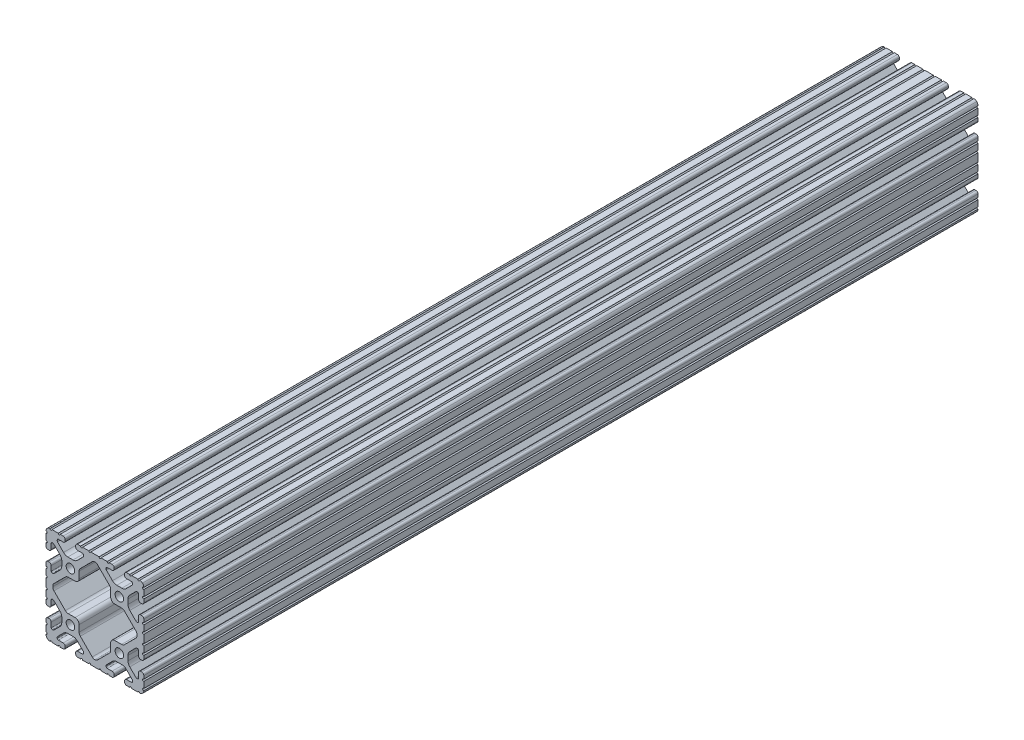
SolidWorks part; units mm, degrees
ref_plane "Front Plane" through (0, 0, 0) normal (0, 0, 1) x (1, 0, 0)
ref_plane "Top Plane" through (0, 0, 0) normal (0, 1, 0) x (1, 0, 0)
ref_plane "Right Plane" through (0, 0, 0) normal (1, 0, 0) x (0, 0, -1)
sketch "Sketch1" plane through (0, 0, 0) normal (0, 0, 1) x (1, 0, 0)
  line L0 (0, 38.1) -> (0, -38.1) construction
  line L1 (-38.1, -38.1) -> (38.1, -38.1) construction
  line L2 (-38.1, -38.1) -> (-38.1, 38.1) construction
  line L3 (-38.1, 38.1) -> (38.1, 38.1) construction
  line L4 (38.1, -38.1) -> (38.1, 38.1) construction
  line L5 (0, 38.1) -> (0, -38.1) construction
  line L6 (-38.1, 0) -> (38.1, 0) construction
  line L7 (-19.05, 19.05) -> (19.05, 19.05) construction
  line L8 (-19.05, 19.05) -> (-19.05, -19.05) construction
  line L9 (-19.05, -19.05) -> (19.05, -19.05) construction
  line L10 (19.05, 19.05) -> (19.05, -19.05) construction
  line L11 (-23.114, 38.1) -> (-23.114, -38.1) construction
  line L12 (-23.114, -38.1) -> (-14.986, 38.1) construction
  line L13 (-14.986, 38.1) -> (-14.986, -38.1) construction
  circle A0 centre (19.05, 19.05) radius 3.3274
  point P0 (0, 0)
  point P9 (0, 0)
  point P12 (-19.05, 0)
  line B0 (-11.3637, -22.8433) -> (-2.0515, -32.1555)
  line B1 (-12.2936, -15.4686) -> (-12.2936, -20.5983)
  line B2 (-20.769, -12.2936) -> (-15.4686, -12.2936)
  line B3 (-31.9021, -2.4756) -> (-23.0141, -11.3637)
  line B4 (-23.0141, 11.3637) -> (-31.9021, 2.4756)
  line B5 (-15.4686, 12.2936) -> (-20.769, 12.2936)
  line B6 (-12.2936, 20.5983) -> (-12.2936, 15.4686)
  line B7 (-2.0515, 32.1555) -> (-11.3637, 22.8433)
  line B8 (11.3637, 22.8433) -> (2.0515, 32.1555)
  line B9 (12.2936, 15.4686) -> (12.2936, 20.5983)
  line B10 (20.769, 12.2936) -> (15.4686, 12.2936)
  line B11 (31.9021, 2.4756) -> (23.0141, 11.3637)
  line B12 (23.0141, -11.3637) -> (31.9021, -2.4756)
  line B13 (15.4686, -12.2936) -> (20.769, -12.2936)
  line B14 (12.2936, -20.5983) -> (12.2936, -15.4686)
  line B15 (2.0515, -32.1555) -> (11.3637, -22.8433)
  line B16 (-4.7773, 38.1) -> (-9.6053, 38.1)
  line B17 (-11.1289, 38.1) -> (-13.4112, 38.1)
  line B18 (-14.986, 36.5252) -> (-14.986, 35.6108)
  line B19 (-13.4112, 34.036) -> (-9.652, 34.036)
  line B20 (-8.763, 33.147) -> (-8.763, 32.4935)
  line B21 (-9.0234, 31.8649) -> (-13.6907, 27.1976)
  line B22 (-17.0493, 25.8064) -> (-21.0507, 25.8064)
  line B23 (-24.4093, 27.1976) -> (-29.1002, 31.8885)
  line B24 (-29.337, 32.7207) -> (-29.337, 33.147)
  line B25 (-28.448, 34.036) -> (-24.6888, 34.036)
  line B26 (-23.114, 35.6108) -> (-23.114, 36.5252)
  line B27 (-24.6888, 38.1) -> (-27.0772, 38.1)
  line B28 (-28.6011, 38.1) -> (-33.4288, 38.1)
  line B29 (-38.1, 33.373) -> (-38.1, 28.5453)
  line B30 (-38.1, 27.0238) -> (-38.1, 24.6302)
  line B31 (-36.5252, 23.0554) -> (-35.6108, 23.0554)
  line B32 (-34.036, 24.6302) -> (-34.036, 28.448)
  line B33 (-33.147, 29.337) -> (-32.6643, 29.337)
  line B34 (-32.0357, 29.0766) -> (-27.1976, 24.2385)
  line B35 (-25.8064, 20.8799) -> (-25.8064, 17.2201)
  line B36 (-27.1976, 13.8615) -> (-31.9489, 9.1101)
  line B37 (-32.7869, 8.763) -> (-33.0603, 8.763)
  line B38 (-34.036, 9.7387) -> (-34.036, 13.4698)
  line B39 (-35.6108, 15.0446) -> (-36.5252, 15.0446)
  line B40 (-38.1, 13.4698) -> (-38.1, 11.075)
  line B41 (-38.1, 9.552) -> (-38.1, 4.7238)
  line B42 (-38.1, 3.2007) -> (-38.1, -3.2007)
  line B43 (-38.1, -4.7238) -> (-38.1, -9.552)
  line B44 (-38.1, -11.075) -> (-38.1, -13.4698)
  line B45 (-36.5252, -15.0446) -> (-35.6108, -15.0446)
  line B46 (-34.036, -13.4698) -> (-34.036, -9.7387)
  line B47 (-33.0603, -8.763) -> (-32.7869, -8.763)
  line B48 (-31.9489, -9.1101) -> (-27.1976, -13.8615)
  line B49 (-25.8064, -17.2201) -> (-25.8064, -20.8799)
  line B50 (-27.1976, -24.2385) -> (-32.0357, -29.0766)
  line B51 (-32.6643, -29.337) -> (-33.147, -29.337)
  line B52 (-34.036, -28.448) -> (-34.036, -24.6302)
  line B53 (-35.6108, -23.0554) -> (-36.5252, -23.0554)
  line B54 (-38.1, -24.6302) -> (-38.1, -27.0238)
  line B55 (-38.1, -28.5453) -> (-38.1, -33.373)
  line B56 (-33.4288, -38.1) -> (-28.6011, -38.1)
  line B57 (-27.0772, -38.1) -> (-24.6888, -38.1)
  line B58 (-23.114, -36.5252) -> (-23.114, -35.6108)
  line B59 (-24.6888, -34.036) -> (-28.448, -34.036)
  line B60 (-29.337, -33.147) -> (-29.337, -32.7207)
  line B61 (-29.1002, -31.8885) -> (-24.4093, -27.1976)
  line B62 (-21.0507, -25.8064) -> (-17.0493, -25.8064)
  line B63 (-13.6907, -27.1976) -> (-9.0234, -31.8649)
  line B64 (-8.763, -32.4935) -> (-8.763, -33.147)
  line B65 (-9.652, -34.036) -> (-13.4112, -34.036)
  line B66 (-14.986, -35.6108) -> (-14.986, -36.5252)
  line B67 (-13.4112, -38.1) -> (-11.1289, -38.1)
  line B68 (-9.6053, -38.1) -> (-4.7773, -38.1)
  line B69 (-3.2537, -38.1) -> (3.2537, -38.1)
  line B70 (4.7773, -38.1) -> (9.6053, -38.1)
  line B71 (11.1289, -38.1) -> (13.4112, -38.1)
  line B72 (14.986, -36.5252) -> (14.986, -35.6108)
  line B73 (13.4112, -34.036) -> (9.652, -34.036)
  line B74 (8.763, -33.147) -> (8.763, -32.4935)
  line B75 (9.0234, -31.8649) -> (13.6907, -27.1976)
  line B76 (17.0493, -25.8064) -> (21.0507, -25.8064)
  line B77 (24.4093, -27.1976) -> (29.1002, -31.8885)
  line B78 (29.337, -32.7207) -> (29.337, -33.147)
  line B79 (28.448, -34.036) -> (24.6888, -34.036)
  line B80 (23.114, -35.6108) -> (23.114, -36.5252)
  line B81 (24.6888, -38.1) -> (27.0772, -38.1)
  line B82 (28.6011, -38.1) -> (33.4288, -38.1)
  line B83 (38.1, -33.373) -> (38.1, -28.5453)
  line B84 (38.1, -27.0238) -> (38.1, -24.6302)
  line B85 (36.5252, -23.0554) -> (35.6108, -23.0554)
  line B86 (34.036, -24.6302) -> (34.036, -28.448)
  line B87 (33.147, -29.337) -> (32.6643, -29.337)
  line B88 (32.0357, -29.0766) -> (27.1976, -24.2385)
  line B89 (25.8064, -20.8799) -> (25.8064, -17.2201)
  line B90 (27.1976, -13.8615) -> (31.9489, -9.1101)
  line B91 (32.7869, -8.763) -> (33.0603, -8.763)
  line B92 (34.036, -9.7387) -> (34.036, -13.4698)
  line B93 (35.6108, -15.0446) -> (36.5252, -15.0446)
  line B94 (38.1, -13.4698) -> (38.1, -11.075)
  line B95 (38.1, -9.552) -> (38.1, -4.7238)
  line B96 (38.1, -3.2007) -> (38.1, 3.2007)
  line B97 (38.1, 4.7238) -> (38.1, 9.552)
  line B98 (38.1, 11.075) -> (38.1, 13.4698)
  line B99 (36.5252, 15.0446) -> (35.6108, 15.0446)
  line B100 (34.036, 13.4698) -> (34.036, 9.7387)
  line B101 (33.0603, 8.763) -> (32.7869, 8.763)
  line B102 (31.9489, 9.1101) -> (27.1976, 13.8615)
  line B103 (25.8064, 17.2201) -> (25.8064, 20.8799)
  line B104 (27.1976, 24.2385) -> (32.0357, 29.0766)
  line B105 (32.6643, 29.337) -> (33.147, 29.337)
  line B106 (34.036, 28.448) -> (34.036, 24.6302)
  line B107 (35.6108, 23.0554) -> (36.5252, 23.0554)
  line B108 (38.1, 24.6302) -> (38.1, 27.0238)
  line B109 (38.1, 28.5453) -> (38.1, 33.373)
  line B110 (33.4288, 38.1) -> (28.6011, 38.1)
  line B111 (27.0772, 38.1) -> (24.6888, 38.1)
  line B112 (23.114, 36.5252) -> (23.114, 35.6108)
  line B113 (24.6888, 34.036) -> (28.448, 34.036)
  line B114 (29.337, 33.147) -> (29.337, 32.7207)
  line B115 (29.1002, 31.8885) -> (24.4093, 27.1976)
  line B116 (21.0507, 25.8064) -> (17.0493, 25.8064)
  line B117 (13.6907, 27.1976) -> (9.0234, 31.8649)
  line B118 (8.763, 32.4935) -> (8.763, 33.147)
  line B119 (9.652, 34.036) -> (13.4112, 34.036)
  line B120 (14.986, 35.6108) -> (14.986, 36.5252)
  line B121 (13.4112, 38.1) -> (11.1289, 38.1)
  line B122 (9.6053, 38.1) -> (4.7773, 38.1)
  line B123 (3.2537, 38.1) -> (-3.2537, 38.1)
  circle B124 centre (-19.05, 19.05) radius 3.3274
  circle B125 centre (-19.05, -19.05) radius 3.3274
  circle B126 centre (19.05, -19.05) radius 3.3274
  circle B127 centre (19.05, 19.05) radius 3.3274
  arc B128 (0, -33.011) -> (2.0515, -32.1555) centre (-0.0139, -30.09) ccw
  arc B129 (-2.0515, -32.1555) -> (0, -33.011) centre (0.0139, -30.09) ccw
  arc B130 (-12.2936, -20.5983) -> (-11.3637, -22.8433) centre (-9.1186, -20.5983) ccw
  arc B131 (-12.2936, -15.4686) -> (-15.4686, -12.2936) centre (-15.4686, -15.4686) ccw
  arc B132 (-23.0141, -11.3637) -> (-20.769, -12.2936) centre (-20.769, -9.1186) ccw
  arc B133 (-32.7287, 0) -> (-31.9021, -2.4756) centre (-29.8367, -0.4102) ccw
  arc B134 (-31.9021, 2.4756) -> (-32.7287, 0) centre (-29.8367, 0.4102) ccw
  arc B135 (-20.769, 12.2936) -> (-23.0141, 11.3637) centre (-20.769, 9.1186) ccw
  arc B136 (-15.4686, 12.2936) -> (-12.2936, 15.4686) centre (-15.4686, 15.4686) ccw
  arc B137 (-11.3637, 22.8433) -> (-12.2936, 20.5983) centre (-9.1186, 20.5983) ccw
  arc B138 (0, 33.011) -> (-2.0515, 32.1555) centre (0.0139, 30.09) ccw
  arc B139 (2.0515, 32.1555) -> (0, 33.011) centre (-0.0139, 30.09) ccw
  arc B140 (12.2936, 20.5983) -> (11.3637, 22.8433) centre (9.1186, 20.5983) ccw
  arc B141 (12.2936, 15.4686) -> (15.4686, 12.2936) centre (15.4686, 15.4686) ccw
  arc B142 (23.0141, 11.3637) -> (20.769, 12.2936) centre (20.769, 9.1186) ccw
  arc B143 (32.7287, 0) -> (31.9021, 2.4756) centre (29.8367, 0.4102) ccw
  arc B144 (31.9021, -2.4756) -> (32.7287, 0) centre (29.8367, -0.4102) ccw
  arc B145 (20.769, -12.2936) -> (23.0141, -11.3637) centre (20.769, -9.1186) ccw
  arc B146 (15.4686, -12.2936) -> (12.2936, -15.4686) centre (15.4686, -15.4686) ccw
  arc B147 (11.3637, -22.8433) -> (12.2936, -20.5983) centre (9.1186, -20.5983) ccw
  arc B148 (-4.7773, 38.1) -> (-3.2537, 38.1) centre (-4.0155, 38.0824) ccw
  arc B149 (-11.1289, 38.1) -> (-9.6053, 38.1) centre (-10.3671, 38.0824) ccw
  arc B150 (-13.4112, 38.1) -> (-14.986, 36.5252) centre (-13.4112, 36.5252) ccw
  arc B151 (-14.986, 35.6108) -> (-13.4112, 34.036) centre (-13.4112, 35.6108) ccw
  arc B152 (-8.763, 33.147) -> (-9.652, 34.036) centre (-9.652, 33.147) ccw
  arc B153 (-9.0234, 31.8649) -> (-8.763, 32.4935) centre (-9.652, 32.4935) ccw
  arc B154 (-17.0493, 25.8064) -> (-13.6907, 27.1976) centre (-17.0493, 30.5562) ccw
  arc B155 (-24.4093, 27.1976) -> (-21.0507, 25.8064) centre (-21.0507, 30.5562) ccw
  arc B156 (-29.337, 32.7207) -> (-29.1002, 31.8885) centre (-28.4716, 32.5172) ccw
  arc B157 (-28.448, 34.036) -> (-29.337, 33.147) centre (-28.448, 33.147) ccw
  arc B158 (-24.6888, 34.036) -> (-23.114, 35.6108) centre (-24.6888, 35.6108) ccw
  arc B159 (-23.114, 36.5252) -> (-24.6888, 38.1) centre (-24.6888, 36.5252) ccw
  arc B160 (-28.6011, 38.1) -> (-27.0772, 38.1) centre (-27.8392, 38.0824) ccw
  arc B161 (-34.9527, 38.1) -> (-33.4288, 38.1) centre (-34.1907, 38.0824) ccw
  arc B162 (-34.9527, 38.1) -> (-37.0861, 37.1826) centre (-34.8521, 34.9266) ccw
  arc B163 (-37.0861, 37.1826) -> (-38.1, 34.8455) centre (-34.925, 34.8566) ccw
  arc B164 (-38.1, 33.373) -> (-38.1, 34.8455) centre (-37.9035, 34.1092) ccw
  arc B165 (-38.1, 27.0238) -> (-38.1, 28.5453) centre (-37.9035, 27.7845) ccw
  arc B166 (-38.1, 24.6302) -> (-36.5252, 23.0554) centre (-36.5252, 24.6302) ccw
  arc B167 (-35.6108, 23.0554) -> (-34.036, 24.6302) centre (-35.6108, 24.6302) ccw
  arc B168 (-33.147, 29.337) -> (-34.036, 28.448) centre (-33.147, 28.448) ccw
  arc B169 (-32.0357, 29.0766) -> (-32.6643, 29.337) centre (-32.6643, 28.448) ccw
  arc B170 (-25.8064, 20.8799) -> (-27.1976, 24.2385) centre (-30.5562, 20.8799) ccw
  arc B171 (-27.1976, 13.8615) -> (-25.8064, 17.2201) centre (-30.5562, 17.2201) ccw
  arc B172 (-32.7869, 8.763) -> (-31.9489, 9.1101) centre (-32.7869, 9.9481) ccw
  arc B173 (-34.036, 9.7387) -> (-33.0603, 8.763) centre (-33.0603, 9.7387) ccw
  arc B174 (-34.036, 13.4698) -> (-35.6108, 15.0446) centre (-35.6108, 13.4698) ccw
  arc B175 (-36.5252, 15.0446) -> (-38.1, 13.4698) centre (-36.5252, 13.4698) ccw
  arc B176 (-38.1, 9.552) -> (-38.1, 11.075) centre (-37.9035, 10.3135) ccw
  arc B177 (-38.1, 3.2007) -> (-38.1, 4.7238) centre (-37.9035, 3.9622) ccw
  arc B178 (-38.1, -4.7238) -> (-38.1, -3.2007) centre (-37.9035, -3.9622) ccw
  arc B179 (-38.1, -11.075) -> (-38.1, -9.552) centre (-37.9035, -10.3135) ccw
  arc B180 (-38.1, -13.4698) -> (-36.5252, -15.0446) centre (-36.5252, -13.4698) ccw
  arc B181 (-35.6108, -15.0446) -> (-34.036, -13.4698) centre (-35.6108, -13.4698) ccw
  arc B182 (-33.0603, -8.763) -> (-34.036, -9.7387) centre (-33.0603, -9.7387) ccw
  arc B183 (-31.9489, -9.1101) -> (-32.7869, -8.763) centre (-32.7869, -9.9481) ccw
  arc B184 (-25.8064, -17.2201) -> (-27.1976, -13.8615) centre (-30.5562, -17.2201) ccw
  arc B185 (-27.1976, -24.2385) -> (-25.8064, -20.8799) centre (-30.5562, -20.8799) ccw
  arc B186 (-32.6643, -29.337) -> (-32.0357, -29.0766) centre (-32.6643, -28.448) ccw
  arc B187 (-34.036, -28.448) -> (-33.147, -29.337) centre (-33.147, -28.448) ccw
  arc B188 (-34.036, -24.6302) -> (-35.6108, -23.0554) centre (-35.6108, -24.6302) ccw
  arc B189 (-36.5252, -23.0554) -> (-38.1, -24.6302) centre (-36.5252, -24.6302) ccw
  arc B190 (-38.1, -28.5453) -> (-38.1, -27.0238) centre (-37.9035, -27.7845) ccw
  arc B191 (-38.1, -34.8455) -> (-38.1, -33.373) centre (-37.9035, -34.1092) ccw
  arc B192 (-38.1, -34.8455) -> (-37.0861, -37.1826) centre (-34.925, -34.8566) ccw
  arc B193 (-37.0861, -37.1826) -> (-34.9527, -38.1) centre (-34.8521, -34.9266) ccw
  arc B194 (-33.4288, -38.1) -> (-34.9527, -38.1) centre (-34.1907, -38.0824) ccw
  arc B195 (-27.0772, -38.1) -> (-28.6011, -38.1) centre (-27.8392, -38.0824) ccw
  arc B196 (-24.6888, -38.1) -> (-23.114, -36.5252) centre (-24.6888, -36.5252) ccw
  arc B197 (-23.114, -35.6108) -> (-24.6888, -34.036) centre (-24.6888, -35.6108) ccw
  arc B198 (-29.337, -33.147) -> (-28.448, -34.036) centre (-28.448, -33.147) ccw
  arc B199 (-29.1002, -31.8885) -> (-29.337, -32.7207) centre (-28.4716, -32.5172) ccw
  arc B200 (-21.0507, -25.8064) -> (-24.4093, -27.1976) centre (-21.0507, -30.5562) ccw
  arc B201 (-13.6907, -27.1976) -> (-17.0493, -25.8064) centre (-17.0493, -30.5562) ccw
  arc B202 (-8.763, -32.4935) -> (-9.0234, -31.8649) centre (-9.652, -32.4935) ccw
  arc B203 (-9.652, -34.036) -> (-8.763, -33.147) centre (-9.652, -33.147) ccw
  arc B204 (-13.4112, -34.036) -> (-14.986, -35.6108) centre (-13.4112, -35.6108) ccw
  arc B205 (-14.986, -36.5252) -> (-13.4112, -38.1) centre (-13.4112, -36.5252) ccw
  arc B206 (-9.6053, -38.1) -> (-11.1289, -38.1) centre (-10.3671, -38.0824) ccw
  arc B207 (-3.2537, -38.1) -> (-4.7773, -38.1) centre (-4.0155, -38.0824) ccw
  arc B208 (4.7773, -38.1) -> (3.2537, -38.1) centre (4.0155, -38.0824) ccw
  arc B209 (11.1289, -38.1) -> (9.6053, -38.1) centre (10.3671, -38.0824) ccw
  arc B210 (13.4112, -38.1) -> (14.986, -36.5252) centre (13.4112, -36.5252) ccw
  arc B211 (14.986, -35.6108) -> (13.4112, -34.036) centre (13.4112, -35.6108) ccw
  arc B212 (8.763, -33.147) -> (9.652, -34.036) centre (9.652, -33.147) ccw
  arc B213 (9.0234, -31.8649) -> (8.763, -32.4935) centre (9.652, -32.4935) ccw
  arc B214 (17.0493, -25.8064) -> (13.6907, -27.1976) centre (17.0493, -30.5562) ccw
  arc B215 (24.4093, -27.1976) -> (21.0507, -25.8064) centre (21.0507, -30.5562) ccw
  arc B216 (29.337, -32.7207) -> (29.1002, -31.8885) centre (28.4716, -32.5172) ccw
  arc B217 (28.448, -34.036) -> (29.337, -33.147) centre (28.448, -33.147) ccw
  arc B218 (24.6888, -34.036) -> (23.114, -35.6108) centre (24.6888, -35.6108) ccw
  arc B219 (23.114, -36.5252) -> (24.6888, -38.1) centre (24.6888, -36.5252) ccw
  arc B220 (28.6011, -38.1) -> (27.0772, -38.1) centre (27.8392, -38.0824) ccw
  arc B221 (34.9527, -38.1) -> (33.4288, -38.1) centre (34.1907, -38.0824) ccw
  arc B222 (34.9527, -38.1) -> (37.0861, -37.1826) centre (34.8521, -34.9266) ccw
  arc B223 (37.0861, -37.1826) -> (38.1, -34.8455) centre (34.925, -34.8566) ccw
  arc B224 (38.1, -33.373) -> (38.1, -34.8455) centre (37.9035, -34.1092) ccw
  arc B225 (38.1, -27.0238) -> (38.1, -28.5453) centre (37.9035, -27.7845) ccw
  arc B226 (38.1, -24.6302) -> (36.5252, -23.0554) centre (36.5252, -24.6302) ccw
  arc B227 (35.6108, -23.0554) -> (34.036, -24.6302) centre (35.6108, -24.6302) ccw
  arc B228 (33.147, -29.337) -> (34.036, -28.448) centre (33.147, -28.448) ccw
  arc B229 (32.0357, -29.0766) -> (32.6643, -29.337) centre (32.6643, -28.448) ccw
  arc B230 (25.8064, -20.8799) -> (27.1976, -24.2385) centre (30.5562, -20.8799) ccw
  arc B231 (27.1976, -13.8615) -> (25.8064, -17.2201) centre (30.5562, -17.2201) ccw
  arc B232 (32.7869, -8.763) -> (31.9489, -9.1101) centre (32.7869, -9.9481) ccw
  arc B233 (34.036, -9.7387) -> (33.0603, -8.763) centre (33.0603, -9.7387) ccw
  arc B234 (34.036, -13.4698) -> (35.6108, -15.0446) centre (35.6108, -13.4698) ccw
  arc B235 (36.5252, -15.0446) -> (38.1, -13.4698) centre (36.5252, -13.4698) ccw
  arc B236 (38.1, -9.552) -> (38.1, -11.075) centre (37.9035, -10.3135) ccw
  arc B237 (38.1, -3.2007) -> (38.1, -4.7238) centre (37.9035, -3.9622) ccw
  arc B238 (38.1, 4.7238) -> (38.1, 3.2007) centre (37.9035, 3.9622) ccw
  arc B239 (38.1, 11.075) -> (38.1, 9.552) centre (37.9035, 10.3135) ccw
  arc B240 (38.1, 13.4698) -> (36.5252, 15.0446) centre (36.5252, 13.4698) ccw
  arc B241 (35.6108, 15.0446) -> (34.036, 13.4698) centre (35.6108, 13.4698) ccw
  arc B242 (33.0603, 8.763) -> (34.036, 9.7387) centre (33.0603, 9.7387) ccw
  arc B243 (31.9489, 9.1101) -> (32.7869, 8.763) centre (32.7869, 9.9481) ccw
  arc B244 (25.8064, 17.2201) -> (27.1976, 13.8615) centre (30.5562, 17.2201) ccw
  arc B245 (27.1976, 24.2385) -> (25.8064, 20.8799) centre (30.5562, 20.8799) ccw
  arc B246 (32.6643, 29.337) -> (32.0357, 29.0766) centre (32.6643, 28.448) ccw
  arc B247 (34.036, 28.448) -> (33.147, 29.337) centre (33.147, 28.448) ccw
  arc B248 (34.036, 24.6302) -> (35.6108, 23.0554) centre (35.6108, 24.6302) ccw
  arc B249 (36.5252, 23.0554) -> (38.1, 24.6302) centre (36.5252, 24.6302) ccw
  arc B250 (38.1, 28.5453) -> (38.1, 27.0238) centre (37.9035, 27.7845) ccw
  arc B251 (38.1, 34.8455) -> (38.1, 33.373) centre (37.9035, 34.1092) ccw
  arc B252 (38.1, 34.8455) -> (37.0861, 37.1826) centre (34.925, 34.8566) ccw
  arc B253 (37.0861, 37.1826) -> (34.9527, 38.1) centre (34.8521, 34.9266) ccw
  arc B254 (33.4288, 38.1) -> (34.9527, 38.1) centre (34.1907, 38.0824) ccw
  arc B255 (27.0772, 38.1) -> (28.6011, 38.1) centre (27.8392, 38.0824) ccw
  arc B256 (24.6888, 38.1) -> (23.114, 36.5252) centre (24.6888, 36.5252) ccw
  arc B257 (23.114, 35.6108) -> (24.6888, 34.036) centre (24.6888, 35.6108) ccw
  arc B258 (29.337, 33.147) -> (28.448, 34.036) centre (28.448, 33.147) ccw
  arc B259 (29.1002, 31.8885) -> (29.337, 32.7207) centre (28.4716, 32.5172) ccw
  arc B260 (21.0507, 25.8064) -> (24.4093, 27.1976) centre (21.0507, 30.5562) ccw
  arc B261 (13.6907, 27.1976) -> (17.0493, 25.8064) centre (17.0493, 30.5562) ccw
  arc B262 (8.763, 32.4935) -> (9.0234, 31.8649) centre (9.652, 32.4935) ccw
  arc B263 (9.652, 34.036) -> (8.763, 33.147) centre (9.652, 33.147) ccw
  arc B264 (13.4112, 34.036) -> (14.986, 35.6108) centre (13.4112, 35.6108) ccw
  arc B265 (14.986, 36.5252) -> (13.4112, 38.1) centre (13.4112, 36.5252) ccw
  arc B266 (9.6053, 38.1) -> (11.1289, 38.1) centre (10.3671, 38.0824) ccw
  arc B267 (3.2537, 38.1) -> (4.7773, 38.1) centre (4.0155, 38.0824) ccw
  dimension "Center Hole Diameter" = 6.6548
  dimension "Rail Width" = 76.2
  dimension "Rail Height" = 76.2
  dimension "T-Slot Width" = 8.128
sketch_block_instance "Block1-1"
sketch_block "Block1"
sketch "Sketch2" plane through (0, 0, 0) normal (1, 0, 0) x (0, 0, -1)
  line L0 (-325, 0) -> (325, 0) construction
  line L1 (-325, 38.1) -> (-325, -38.1) construction
  line L2 (-325, -38.1) -> (325, -38.1) construction
  line L3 (325, -38.1) -> (325, 38.1) construction
  line L4 (-223.4, 0) -> (-223.4, 38.1) construction
  line L5 (-223.4, 38.1) -> (223.4, 38.1) construction
  line L6 (223.4, 38.1) -> (223.4, 0) construction
  point P5 (223.4, 0)
  point P10 (-223.4, 0)
  dimension "D1" = 101.6
  dimension "Length" = 650
  dimension "D2" = 101.6
sketch "Sketch3" plane through (0, 0, 0) normal (0, 0, 1) x (1, 0, 0)
  line L0 (-11.3637, -22.8433) -> (-2.0515, -32.1555) construction
  line L1 (-12.2936, -15.4686) -> (-12.2936, -20.5983) construction
  line L2 (-20.769, -12.2936) -> (-15.4686, -12.2936) construction
  line L3 (-31.9021, -2.4756) -> (-23.0141, -11.3637) construction
  line L4 (-23.0141, 11.3637) -> (-31.9021, 2.4756) construction
  line L5 (-15.4686, 12.2936) -> (-20.769, 12.2936) construction
  line L6 (-12.2936, 20.5983) -> (-12.2936, 15.4686) construction
  line L7 (-2.0515, 32.1555) -> (-11.3637, 22.8433) construction
  line L8 (11.3637, 22.8433) -> (2.0515, 32.1555) construction
  line L9 (12.2936, 15.4686) -> (12.2936, 20.5983) construction
  line L10 (20.769, 12.2936) -> (15.4686, 12.2936) construction
  line L11 (31.9021, 2.4756) -> (23.0141, 11.3637) construction
  line L12 (23.0141, -11.3637) -> (31.9021, -2.4756) construction
  line L13 (15.4686, -12.2936) -> (20.769, -12.2936) construction
  line L14 (12.2936, -20.5983) -> (12.2936, -15.4686) construction
  line L15 (2.0515, -32.1555) -> (11.3637, -22.8433) construction
  line L16 (34.036, 28.448) -> (34.036, 24.6302) construction
  line L17 (35.6108, 23.0554) -> (36.5252, 23.0554) construction
  line L18 (38.1, 24.6302) -> (38.1, 27.0238) construction
  line L19 (38.1, 28.5453) -> (38.1, 33.373) construction
  line L20 (33.4288, 38.1) -> (28.6011, 38.1) construction
  line L21 (27.0772, 38.1) -> (24.6888, 38.1) construction
  line L22 (23.114, 36.5252) -> (23.114, 35.6108) construction
  line L23 (24.6888, 34.036) -> (28.448, 34.036) construction
  line L24 (29.337, 33.147) -> (29.337, 32.7207) construction
  line L25 (29.1002, 31.8885) -> (24.4093, 27.1976) construction
  line L26 (21.0507, 25.8064) -> (17.0493, 25.8064) construction
  line L27 (13.6907, 27.1976) -> (9.0234, 31.8649) construction
  line L28 (8.763, 32.4935) -> (8.763, 33.147) construction
  line L29 (9.652, 34.036) -> (13.4112, 34.036) construction
  line L30 (14.986, 35.6108) -> (14.986, 36.5252) construction
  line L31 (13.4112, 38.1) -> (11.1289, 38.1) construction
  line L32 (9.6053, 38.1) -> (4.7773, 38.1) construction
  line L33 (3.2537, 38.1) -> (-3.2537, 38.1) construction
  line L34 (-4.7773, 38.1) -> (-9.6053, 38.1) construction
  line L35 (-11.1289, 38.1) -> (-13.4112, 38.1) construction
  line L36 (-14.986, 36.5252) -> (-14.986, 35.6108) construction
  line L37 (-13.4112, 34.036) -> (-9.652, 34.036) construction
  line L38 (-8.763, 33.147) -> (-8.763, 32.4935) construction
  line L39 (-9.0234, 31.8649) -> (-13.6907, 27.1976) construction
  line L40 (-17.0493, 25.8064) -> (-21.0507, 25.8064) construction
  line L41 (-24.4093, 27.1976) -> (-29.1002, 31.8885) construction
  line L42 (-29.337, 32.7207) -> (-29.337, 33.147) construction
  line L43 (-28.448, 34.036) -> (-24.6888, 34.036) construction
  line L44 (-23.114, 35.6108) -> (-23.114, 36.5252) construction
  line L45 (-24.6888, 38.1) -> (-27.0772, 38.1) construction
  line L46 (-28.6011, 38.1) -> (-33.4288, 38.1) construction
  line L47 (-38.1, 33.373) -> (-38.1, 28.5453) construction
  line L48 (-38.1, 27.0238) -> (-38.1, 24.6302) construction
  line L49 (-36.5252, 23.0554) -> (-35.6108, 23.0554) construction
  line L50 (-34.036, 24.6302) -> (-34.036, 28.448) construction
  line L51 (-33.147, 29.337) -> (-32.6643, 29.337) construction
  line L52 (-32.0357, 29.0766) -> (-27.1976, 24.2385) construction
  line L53 (-25.8064, 20.8799) -> (-25.8064, 17.2201) construction
  line L54 (-27.1976, 13.8615) -> (-31.9489, 9.1101) construction
  line L55 (-32.7869, 8.763) -> (-33.0603, 8.763) construction
  line L56 (-34.036, 9.7387) -> (-34.036, 13.4698) construction
  line L57 (-35.6108, 15.0446) -> (-36.5252, 15.0446) construction
  line L58 (-38.1, 13.4698) -> (-38.1, 11.075) construction
  line L59 (-38.1, 9.552) -> (-38.1, 4.7238) construction
  line L60 (-38.1, 3.2007) -> (-38.1, -3.2007) construction
  line L61 (-38.1, -4.7238) -> (-38.1, -9.552) construction
  line L62 (-38.1, -11.075) -> (-38.1, -13.4698) construction
  line L63 (-36.5252, -15.0446) -> (-35.6108, -15.0446) construction
  line L64 (-34.036, -13.4698) -> (-34.036, -9.7387) construction
  line L65 (-33.0603, -8.763) -> (-32.7869, -8.763) construction
  line L66 (-31.9489, -9.1101) -> (-27.1976, -13.8615) construction
  line L67 (-25.8064, -17.2201) -> (-25.8064, -20.8799) construction
  line L68 (-27.1976, -24.2385) -> (-32.0357, -29.0766) construction
  line L69 (-32.6643, -29.337) -> (-33.147, -29.337) construction
  line L70 (-34.036, -28.448) -> (-34.036, -24.6302) construction
  line L71 (-35.6108, -23.0554) -> (-36.5252, -23.0554) construction
  line L72 (-38.1, -24.6302) -> (-38.1, -27.0238) construction
  line L73 (-38.1, -28.5453) -> (-38.1, -33.373) construction
  line L74 (-33.4288, -38.1) -> (-28.6011, -38.1) construction
  line L75 (-27.0772, -38.1) -> (-24.6888, -38.1) construction
  line L76 (-23.114, -36.5252) -> (-23.114, -35.6108) construction
  line L77 (-24.6888, -34.036) -> (-28.448, -34.036) construction
  line L78 (-29.337, -33.147) -> (-29.337, -32.7207) construction
  line L79 (-29.1002, -31.8885) -> (-24.4093, -27.1976) construction
  line L80 (-21.0507, -25.8064) -> (-17.0493, -25.8064) construction
  line L81 (-13.6907, -27.1976) -> (-9.0234, -31.8649) construction
  line L82 (-8.763, -32.4935) -> (-8.763, -33.147) construction
  line L83 (-9.652, -34.036) -> (-13.4112, -34.036) construction
  line L84 (-14.986, -35.6108) -> (-14.986, -36.5252) construction
  line L85 (-13.4112, -38.1) -> (-11.1289, -38.1) construction
  line L86 (-9.6053, -38.1) -> (-4.7773, -38.1) construction
  line L87 (-3.2537, -38.1) -> (3.2537, -38.1) construction
  line L88 (4.7773, -38.1) -> (9.6053, -38.1) construction
  line L89 (11.1289, -38.1) -> (13.4112, -38.1) construction
  line L90 (14.986, -36.5252) -> (14.986, -35.6108) construction
  line L91 (13.4112, -34.036) -> (9.652, -34.036) construction
  line L92 (8.763, -33.147) -> (8.763, -32.4935) construction
  line L93 (9.0234, -31.8649) -> (13.6907, -27.1976) construction
  line L94 (17.0493, -25.8064) -> (21.0507, -25.8064) construction
  line L95 (24.4093, -27.1976) -> (29.1002, -31.8885) construction
  line L96 (29.337, -32.7207) -> (29.337, -33.147) construction
  line L97 (28.448, -34.036) -> (24.6888, -34.036) construction
  line L98 (23.114, -35.6108) -> (23.114, -36.5252) construction
  line L99 (24.6888, -38.1) -> (27.0772, -38.1) construction
  line L100 (28.6011, -38.1) -> (33.4288, -38.1) construction
  line L101 (38.1, -33.373) -> (38.1, -28.5453) construction
  line L102 (38.1, -27.0238) -> (38.1, -24.6302) construction
  line L103 (36.5252, -23.0554) -> (35.6108, -23.0554) construction
  line L104 (34.036, -24.6302) -> (34.036, -28.448) construction
  line L105 (33.147, -29.337) -> (32.6643, -29.337) construction
  line L106 (32.0357, -29.0766) -> (27.1976, -24.2385) construction
  line L107 (25.8064, -20.8799) -> (25.8064, -17.2201) construction
  line L108 (27.1976, -13.8615) -> (31.9489, -9.1101) construction
  line L109 (32.7869, -8.763) -> (33.0603, -8.763) construction
  line L110 (34.036, -9.7387) -> (34.036, -13.4698) construction
  line L111 (35.6108, -15.0446) -> (36.5252, -15.0446) construction
  line L112 (38.1, -13.4698) -> (38.1, -11.075) construction
  line L113 (38.1, -9.552) -> (38.1, -4.7238) construction
  line L114 (38.1, -3.2007) -> (38.1, 3.2007) construction
  line L115 (38.1, 4.7238) -> (38.1, 9.552) construction
  line L116 (38.1, 11.075) -> (38.1, 13.4698) construction
  line L117 (36.5252, 15.0446) -> (35.6108, 15.0446) construction
  line L118 (34.036, 13.4698) -> (34.036, 9.7387) construction
  line L119 (33.0603, 8.763) -> (32.7869, 8.763) construction
  line L120 (31.9489, 9.1101) -> (27.1976, 13.8615) construction
  line L121 (25.8064, 17.2201) -> (25.8064, 20.8799) construction
  line L122 (27.1976, 24.2385) -> (32.0357, 29.0766) construction
  line L123 (32.6643, 29.337) -> (33.147, 29.337) construction
  line L124 (-11.3637, -22.8433) -> (-2.0515, -32.1555)
  line L125 (-12.2936, -15.4686) -> (-12.2936, -20.5983)
  line L126 (-20.769, -12.2936) -> (-15.4686, -12.2936)
  line L127 (-31.9021, -2.4756) -> (-23.0141, -11.3637)
  line L128 (-23.0141, 11.3637) -> (-31.9021, 2.4756)
  line L129 (-15.4686, 12.2936) -> (-20.769, 12.2936)
  line L130 (-12.2936, 20.5983) -> (-12.2936, 15.4686)
  line L131 (-2.0515, 32.1555) -> (-11.3637, 22.8433)
  line L132 (11.3637, 22.8433) -> (2.0515, 32.1555)
  line L133 (12.2936, 15.4686) -> (12.2936, 20.5983)
  line L134 (20.769, 12.2936) -> (15.4686, 12.2936)
  line L135 (31.9021, 2.4756) -> (23.0141, 11.3637)
  line L136 (23.0141, -11.3637) -> (31.9021, -2.4756)
  line L137 (15.4686, -12.2936) -> (20.769, -12.2936)
  line L138 (12.2936, -20.5983) -> (12.2936, -15.4686)
  line L139 (2.0515, -32.1555) -> (11.3637, -22.8433)
  line L140 (34.036, 28.448) -> (34.036, 24.6302)
  line L141 (35.6108, 23.0554) -> (36.5252, 23.0554)
  line L142 (38.1, 24.6302) -> (38.1, 27.0238)
  line L143 (38.1, 28.5453) -> (38.1, 33.373)
  line L144 (33.4288, 38.1) -> (28.6011, 38.1)
  line L145 (27.0772, 38.1) -> (24.6888, 38.1)
  line L146 (23.114, 36.5252) -> (23.114, 35.6108)
  line L147 (24.6888, 34.036) -> (28.448, 34.036)
  line L148 (29.337, 33.147) -> (29.337, 32.7207)
  line L149 (29.1002, 31.8885) -> (24.4093, 27.1976)
  line L150 (21.0507, 25.8064) -> (17.0493, 25.8064)
  line L151 (13.6907, 27.1976) -> (9.0234, 31.8649)
  line L152 (8.763, 32.4935) -> (8.763, 33.147)
  line L153 (9.652, 34.036) -> (13.4112, 34.036)
  line L154 (14.986, 35.6108) -> (14.986, 36.5252)
  line L155 (13.4112, 38.1) -> (11.1289, 38.1)
  line L156 (9.6053, 38.1) -> (4.7773, 38.1)
  line L157 (3.2537, 38.1) -> (-3.2537, 38.1)
  line L158 (-4.7773, 38.1) -> (-9.6053, 38.1)
  line L159 (-11.1289, 38.1) -> (-13.4112, 38.1)
  line L160 (-14.986, 36.5252) -> (-14.986, 35.6108)
  line L161 (-13.4112, 34.036) -> (-9.652, 34.036)
  line L162 (-8.763, 33.147) -> (-8.763, 32.4935)
  line L163 (-9.0234, 31.8649) -> (-13.6907, 27.1976)
  line L164 (-17.0493, 25.8064) -> (-21.0507, 25.8064)
  line L165 (-24.4093, 27.1976) -> (-29.1002, 31.8885)
  line L166 (-29.337, 32.7207) -> (-29.337, 33.147)
  line L167 (-28.448, 34.036) -> (-24.6888, 34.036)
  line L168 (-23.114, 35.6108) -> (-23.114, 36.5252)
  line L169 (-24.6888, 38.1) -> (-27.0772, 38.1)
  line L170 (-28.6011, 38.1) -> (-33.4288, 38.1)
  line L171 (-38.1, 33.373) -> (-38.1, 28.5453)
  line L172 (-38.1, 27.0238) -> (-38.1, 24.6302)
  line L173 (-36.5252, 23.0554) -> (-35.6108, 23.0554)
  line L174 (-34.036, 24.6302) -> (-34.036, 28.448)
  line L175 (-33.147, 29.337) -> (-32.6643, 29.337)
  line L176 (-32.0357, 29.0766) -> (-27.1976, 24.2385)
  line L177 (-25.8064, 20.8799) -> (-25.8064, 17.2201)
  line L178 (-27.1976, 13.8615) -> (-31.9489, 9.1101)
  line L179 (-32.7869, 8.763) -> (-33.0603, 8.763)
  line L180 (-34.036, 9.7387) -> (-34.036, 13.4698)
  line L181 (-35.6108, 15.0446) -> (-36.5252, 15.0446)
  line L182 (-38.1, 13.4698) -> (-38.1, 11.075)
  line L183 (-38.1, 9.552) -> (-38.1, 4.7238)
  line L184 (-38.1, 3.2007) -> (-38.1, -3.2007)
  line L185 (-38.1, -4.7238) -> (-38.1, -9.552)
  line L186 (-38.1, -11.075) -> (-38.1, -13.4698)
  line L187 (-36.5252, -15.0446) -> (-35.6108, -15.0446)
  line L188 (-34.036, -13.4698) -> (-34.036, -9.7387)
  line L189 (-33.0603, -8.763) -> (-32.7869, -8.763)
  line L190 (-31.9489, -9.1101) -> (-27.1976, -13.8615)
  line L191 (-25.8064, -17.2201) -> (-25.8064, -20.8799)
  line L192 (-27.1976, -24.2385) -> (-32.0357, -29.0766)
  line L193 (-32.6643, -29.337) -> (-33.147, -29.337)
  line L194 (-34.036, -28.448) -> (-34.036, -24.6302)
  line L195 (-35.6108, -23.0554) -> (-36.5252, -23.0554)
  line L196 (-38.1, -24.6302) -> (-38.1, -27.0238)
  line L197 (-38.1, -28.5453) -> (-38.1, -33.373)
  line L198 (-33.4288, -38.1) -> (-28.6011, -38.1)
  line L199 (-27.0772, -38.1) -> (-24.6888, -38.1)
  line L200 (-23.114, -36.5252) -> (-23.114, -35.6108)
  line L201 (-24.6888, -34.036) -> (-28.448, -34.036)
  line L202 (-29.337, -33.147) -> (-29.337, -32.7207)
  line L203 (-29.1002, -31.8885) -> (-24.4093, -27.1976)
  line L204 (-21.0507, -25.8064) -> (-17.0493, -25.8064)
  line L205 (-13.6907, -27.1976) -> (-9.0234, -31.8649)
  line L206 (-8.763, -32.4935) -> (-8.763, -33.147)
  line L207 (-9.652, -34.036) -> (-13.4112, -34.036)
  line L208 (-14.986, -35.6108) -> (-14.986, -36.5252)
  line L209 (-13.4112, -38.1) -> (-11.1289, -38.1)
  line L210 (-9.6053, -38.1) -> (-4.7773, -38.1)
  line L211 (-3.2537, -38.1) -> (3.2537, -38.1)
  line L212 (4.7773, -38.1) -> (9.6053, -38.1)
  line L213 (11.1289, -38.1) -> (13.4112, -38.1)
  line L214 (14.986, -36.5252) -> (14.986, -35.6108)
  line L215 (13.4112, -34.036) -> (9.652, -34.036)
  line L216 (8.763, -33.147) -> (8.763, -32.4935)
  line L217 (9.0234, -31.8649) -> (13.6907, -27.1976)
  line L218 (17.0493, -25.8064) -> (21.0507, -25.8064)
  line L219 (24.4093, -27.1976) -> (29.1002, -31.8885)
  line L220 (29.337, -32.7207) -> (29.337, -33.147)
  line L221 (28.448, -34.036) -> (24.6888, -34.036)
  line L222 (23.114, -35.6108) -> (23.114, -36.5252)
  line L223 (24.6888, -38.1) -> (27.0772, -38.1)
  line L224 (28.6011, -38.1) -> (33.4288, -38.1)
  line L225 (38.1, -33.373) -> (38.1, -28.5453)
  line L226 (38.1, -27.0238) -> (38.1, -24.6302)
  line L227 (36.5252, -23.0554) -> (35.6108, -23.0554)
  line L228 (34.036, -24.6302) -> (34.036, -28.448)
  line L229 (33.147, -29.337) -> (32.6643, -29.337)
  line L230 (32.0357, -29.0766) -> (27.1976, -24.2385)
  line L231 (25.8064, -20.8799) -> (25.8064, -17.2201)
  line L232 (27.1976, -13.8615) -> (31.9489, -9.1101)
  line L233 (32.7869, -8.763) -> (33.0603, -8.763)
  line L234 (34.036, -9.7387) -> (34.036, -13.4698)
  line L235 (35.6108, -15.0446) -> (36.5252, -15.0446)
  line L236 (38.1, -13.4698) -> (38.1, -11.075)
  line L237 (38.1, -9.552) -> (38.1, -4.7238)
  line L238 (38.1, -3.2007) -> (38.1, 3.2007)
  line L239 (38.1, 4.7238) -> (38.1, 9.552)
  line L240 (38.1, 11.075) -> (38.1, 13.4698)
  line L241 (36.5252, 15.0446) -> (35.6108, 15.0446)
  line L242 (34.036, 13.4698) -> (34.036, 9.7387)
  line L243 (33.0603, 8.763) -> (32.7869, 8.763)
  line L244 (31.9489, 9.1101) -> (27.1976, 13.8615)
  line L245 (25.8064, 17.2201) -> (25.8064, 20.8799)
  line L246 (27.1976, 24.2385) -> (32.0357, 29.0766)
  line L247 (32.6643, 29.337) -> (33.147, 29.337)
  arc A0 (-2.0515, -32.1555) -> (0, -33.011) centre (0.0139, -30.09) ccw construction
  circle A1 centre (19.05, 19.05) radius 3.3274
  circle A2 centre (19.05, 19.05) radius 3.3274
  arc A3 (-12.2936, -20.5983) -> (-11.3637, -22.8433) centre (-9.1186, -20.5983) ccw construction
  arc A4 (-12.2936, -15.4686) -> (-15.4686, -12.2936) centre (-15.4686, -15.4686) ccw construction
  arc A5 (-23.0141, -11.3637) -> (-20.769, -12.2936) centre (-20.769, -9.1186) ccw construction
  arc A6 (-32.7287, 0) -> (-31.9021, -2.4756) centre (-29.8367, -0.4102) ccw construction
  arc A7 (-31.9021, 2.4756) -> (-32.7287, 0) centre (-29.8367, 0.4102) ccw construction
  arc A8 (-20.769, 12.2936) -> (-23.0141, 11.3637) centre (-20.769, 9.1186) ccw construction
  arc A9 (-15.4686, 12.2936) -> (-12.2936, 15.4686) centre (-15.4686, 15.4686) ccw construction
  arc A10 (-11.3637, 22.8433) -> (-12.2936, 20.5983) centre (-9.1186, 20.5983) ccw construction
  arc A11 (0, 33.011) -> (-2.0515, 32.1555) centre (0.0139, 30.09) ccw construction
  arc A12 (2.0515, 32.1555) -> (0, 33.011) centre (-0.0139, 30.09) ccw construction
  arc A13 (12.2936, 20.5983) -> (11.3637, 22.8433) centre (9.1186, 20.5983) ccw construction
  arc A14 (12.2936, 15.4686) -> (15.4686, 12.2936) centre (15.4686, 15.4686) ccw construction
  arc A15 (23.0141, 11.3637) -> (20.769, 12.2936) centre (20.769, 9.1186) ccw construction
  arc A16 (32.7287, 0) -> (31.9021, 2.4756) centre (29.8367, 0.4102) ccw construction
  arc A17 (31.9021, -2.4756) -> (32.7287, 0) centre (29.8367, -0.4102) ccw construction
  arc A18 (20.769, -12.2936) -> (23.0141, -11.3637) centre (20.769, -9.1186) ccw construction
  arc A19 (15.4686, -12.2936) -> (12.2936, -15.4686) centre (15.4686, -15.4686) ccw construction
  arc A20 (11.3637, -22.8433) -> (12.2936, -20.5983) centre (9.1186, -20.5983) ccw construction
  arc A21 (0, -33.011) -> (2.0515, -32.1555) centre (-0.0139, -30.09) ccw construction
  circle A22 centre (-19.05, 19.05) radius 3.3274 construction
  circle A23 centre (19.05, -19.05) radius 3.3274 construction
  circle A24 centre (-19.05, -19.05) radius 3.3274 construction
  circle A25 centre (19.05, 19.05) radius 3.3274 construction
  arc A26 (34.036, 24.6302) -> (35.6108, 23.0554) centre (35.6108, 24.6302) ccw construction
  arc A27 (36.5252, 23.0554) -> (38.1, 24.6302) centre (36.5252, 24.6302) ccw construction
  arc A28 (38.1, 28.5453) -> (38.1, 27.0238) centre (37.9035, 27.7845) ccw construction
  arc A29 (38.1, 34.8455) -> (38.1, 33.373) centre (37.9035, 34.1092) ccw construction
  arc A30 (38.1, 34.8455) -> (37.0861, 37.1826) centre (34.925, 34.8566) ccw construction
  arc A31 (37.0861, 37.1826) -> (34.9527, 38.1) centre (34.8521, 34.9266) ccw construction
  arc A32 (33.4288, 38.1) -> (34.9527, 38.1) centre (34.1907, 38.0824) ccw construction
  arc A33 (27.0772, 38.1) -> (28.6011, 38.1) centre (27.8392, 38.0824) ccw construction
  arc A34 (24.6888, 38.1) -> (23.114, 36.5252) centre (24.6888, 36.5252) ccw construction
  arc A35 (23.114, 35.6108) -> (24.6888, 34.036) centre (24.6888, 35.6108) ccw construction
  arc A36 (29.337, 33.147) -> (28.448, 34.036) centre (28.448, 33.147) ccw construction
  arc A37 (29.1002, 31.8885) -> (29.337, 32.7207) centre (28.4716, 32.5172) ccw construction
  arc A38 (21.0507, 25.8064) -> (24.4093, 27.1976) centre (21.0507, 30.5562) ccw construction
  arc A39 (13.6907, 27.1976) -> (17.0493, 25.8064) centre (17.0493, 30.5562) ccw construction
  arc A40 (8.763, 32.4935) -> (9.0234, 31.8649) centre (9.652, 32.4935) ccw construction
  arc A41 (9.652, 34.036) -> (8.763, 33.147) centre (9.652, 33.147) ccw construction
  arc A42 (13.4112, 34.036) -> (14.986, 35.6108) centre (13.4112, 35.6108) ccw construction
  arc A43 (14.986, 36.5252) -> (13.4112, 38.1) centre (13.4112, 36.5252) ccw construction
  arc A44 (9.6053, 38.1) -> (11.1289, 38.1) centre (10.3671, 38.0824) ccw construction
  arc A45 (3.2537, 38.1) -> (4.7773, 38.1) centre (4.0155, 38.0824) ccw construction
  arc A46 (-4.7773, 38.1) -> (-3.2537, 38.1) centre (-4.0155, 38.0824) ccw construction
  arc A47 (-11.1289, 38.1) -> (-9.6053, 38.1) centre (-10.3671, 38.0824) ccw construction
  arc A48 (-13.4112, 38.1) -> (-14.986, 36.5252) centre (-13.4112, 36.5252) ccw construction
  arc A49 (-14.986, 35.6108) -> (-13.4112, 34.036) centre (-13.4112, 35.6108) ccw construction
  arc A50 (-8.763, 33.147) -> (-9.652, 34.036) centre (-9.652, 33.147) ccw construction
  arc A51 (-9.0234, 31.8649) -> (-8.763, 32.4935) centre (-9.652, 32.4935) ccw construction
  arc A52 (-17.0493, 25.8064) -> (-13.6907, 27.1976) centre (-17.0493, 30.5562) ccw construction
  arc A53 (-24.4093, 27.1976) -> (-21.0507, 25.8064) centre (-21.0507, 30.5562) ccw construction
  arc A54 (-29.337, 32.7207) -> (-29.1002, 31.8885) centre (-28.4716, 32.5172) ccw construction
  arc A55 (-28.448, 34.036) -> (-29.337, 33.147) centre (-28.448, 33.147) ccw construction
  arc A56 (-24.6888, 34.036) -> (-23.114, 35.6108) centre (-24.6888, 35.6108) ccw construction
  arc A57 (-23.114, 36.5252) -> (-24.6888, 38.1) centre (-24.6888, 36.5252) ccw construction
  arc A58 (-28.6011, 38.1) -> (-27.0772, 38.1) centre (-27.8392, 38.0824) ccw construction
  arc A59 (-34.9527, 38.1) -> (-33.4288, 38.1) centre (-34.1907, 38.0824) ccw construction
  arc A60 (-34.9527, 38.1) -> (-37.0861, 37.1826) centre (-34.8521, 34.9266) ccw construction
  arc A61 (-37.0861, 37.1826) -> (-38.1, 34.8455) centre (-34.925, 34.8566) ccw construction
  arc A62 (-38.1, 33.373) -> (-38.1, 34.8455) centre (-37.9035, 34.1092) ccw construction
  arc A63 (-38.1, 27.0238) -> (-38.1, 28.5453) centre (-37.9035, 27.7845) ccw construction
  arc A64 (-38.1, 24.6302) -> (-36.5252, 23.0554) centre (-36.5252, 24.6302) ccw construction
  arc A65 (-35.6108, 23.0554) -> (-34.036, 24.6302) centre (-35.6108, 24.6302) ccw construction
  arc A66 (-33.147, 29.337) -> (-34.036, 28.448) centre (-33.147, 28.448) ccw construction
  arc A67 (-32.0357, 29.0766) -> (-32.6643, 29.337) centre (-32.6643, 28.448) ccw construction
  arc A68 (-25.8064, 20.8799) -> (-27.1976, 24.2385) centre (-30.5562, 20.8799) ccw construction
  arc A69 (-27.1976, 13.8615) -> (-25.8064, 17.2201) centre (-30.5562, 17.2201) ccw construction
  arc A70 (-32.7869, 8.763) -> (-31.9489, 9.1101) centre (-32.7869, 9.9481) ccw construction
  arc A71 (-34.036, 9.7387) -> (-33.0603, 8.763) centre (-33.0603, 9.7387) ccw construction
  arc A72 (-34.036, 13.4698) -> (-35.6108, 15.0446) centre (-35.6108, 13.4698) ccw construction
  arc A73 (-36.5252, 15.0446) -> (-38.1, 13.4698) centre (-36.5252, 13.4698) ccw construction
  arc A74 (-38.1, 9.552) -> (-38.1, 11.075) centre (-37.9035, 10.3135) ccw construction
  arc A75 (-38.1, 3.2007) -> (-38.1, 4.7238) centre (-37.9035, 3.9622) ccw construction
  arc A76 (-38.1, -4.7238) -> (-38.1, -3.2007) centre (-37.9035, -3.9622) ccw construction
  arc A77 (-38.1, -11.075) -> (-38.1, -9.552) centre (-37.9035, -10.3135) ccw construction
  arc A78 (-38.1, -13.4698) -> (-36.5252, -15.0446) centre (-36.5252, -13.4698) ccw construction
  arc A79 (-35.6108, -15.0446) -> (-34.036, -13.4698) centre (-35.6108, -13.4698) ccw construction
  arc A80 (-33.0603, -8.763) -> (-34.036, -9.7387) centre (-33.0603, -9.7387) ccw construction
  arc A81 (-31.9489, -9.1101) -> (-32.7869, -8.763) centre (-32.7869, -9.9481) ccw construction
  arc A82 (-25.8064, -17.2201) -> (-27.1976, -13.8615) centre (-30.5562, -17.2201) ccw construction
  arc A83 (-27.1976, -24.2385) -> (-25.8064, -20.8799) centre (-30.5562, -20.8799) ccw construction
  arc A84 (-32.6643, -29.337) -> (-32.0357, -29.0766) centre (-32.6643, -28.448) ccw construction
  arc A85 (-34.036, -28.448) -> (-33.147, -29.337) centre (-33.147, -28.448) ccw construction
  arc A86 (-34.036, -24.6302) -> (-35.6108, -23.0554) centre (-35.6108, -24.6302) ccw construction
  arc A87 (-36.5252, -23.0554) -> (-38.1, -24.6302) centre (-36.5252, -24.6302) ccw construction
  arc A88 (-38.1, -28.5453) -> (-38.1, -27.0238) centre (-37.9035, -27.7845) ccw construction
  arc A89 (-38.1, -34.8455) -> (-38.1, -33.373) centre (-37.9035, -34.1092) ccw construction
  arc A90 (-38.1, -34.8455) -> (-37.0861, -37.1826) centre (-34.925, -34.8566) ccw construction
  arc A91 (-37.0861, -37.1826) -> (-34.9527, -38.1) centre (-34.8521, -34.9266) ccw construction
  arc A92 (-33.4288, -38.1) -> (-34.9527, -38.1) centre (-34.1907, -38.0824) ccw construction
  arc A93 (-27.0772, -38.1) -> (-28.6011, -38.1) centre (-27.8392, -38.0824) ccw construction
  arc A94 (-24.6888, -38.1) -> (-23.114, -36.5252) centre (-24.6888, -36.5252) ccw construction
  arc A95 (-23.114, -35.6108) -> (-24.6888, -34.036) centre (-24.6888, -35.6108) ccw construction
  arc A96 (-29.337, -33.147) -> (-28.448, -34.036) centre (-28.448, -33.147) ccw construction
  arc A97 (-29.1002, -31.8885) -> (-29.337, -32.7207) centre (-28.4716, -32.5172) ccw construction
  arc A98 (-21.0507, -25.8064) -> (-24.4093, -27.1976) centre (-21.0507, -30.5562) ccw construction
  arc A99 (-13.6907, -27.1976) -> (-17.0493, -25.8064) centre (-17.0493, -30.5562) ccw construction
  arc A100 (-8.763, -32.4935) -> (-9.0234, -31.8649) centre (-9.652, -32.4935) ccw construction
  arc A101 (-9.652, -34.036) -> (-8.763, -33.147) centre (-9.652, -33.147) ccw construction
  arc A102 (-13.4112, -34.036) -> (-14.986, -35.6108) centre (-13.4112, -35.6108) ccw construction
  arc A103 (-14.986, -36.5252) -> (-13.4112, -38.1) centre (-13.4112, -36.5252) ccw construction
  arc A104 (-9.6053, -38.1) -> (-11.1289, -38.1) centre (-10.3671, -38.0824) ccw construction
  arc A105 (-3.2537, -38.1) -> (-4.7773, -38.1) centre (-4.0155, -38.0824) ccw construction
  arc A106 (4.7773, -38.1) -> (3.2537, -38.1) centre (4.0155, -38.0824) ccw construction
  arc A107 (11.1289, -38.1) -> (9.6053, -38.1) centre (10.3671, -38.0824) ccw construction
  arc A108 (13.4112, -38.1) -> (14.986, -36.5252) centre (13.4112, -36.5252) ccw construction
  arc A109 (14.986, -35.6108) -> (13.4112, -34.036) centre (13.4112, -35.6108) ccw construction
  arc A110 (8.763, -33.147) -> (9.652, -34.036) centre (9.652, -33.147) ccw construction
  arc A111 (9.0234, -31.8649) -> (8.763, -32.4935) centre (9.652, -32.4935) ccw construction
  arc A112 (17.0493, -25.8064) -> (13.6907, -27.1976) centre (17.0493, -30.5562) ccw construction
  arc A113 (24.4093, -27.1976) -> (21.0507, -25.8064) centre (21.0507, -30.5562) ccw construction
  arc A114 (29.337, -32.7207) -> (29.1002, -31.8885) centre (28.4716, -32.5172) ccw construction
  arc A115 (28.448, -34.036) -> (29.337, -33.147) centre (28.448, -33.147) ccw construction
  arc A116 (24.6888, -34.036) -> (23.114, -35.6108) centre (24.6888, -35.6108) ccw construction
  arc A117 (23.114, -36.5252) -> (24.6888, -38.1) centre (24.6888, -36.5252) ccw construction
  arc A118 (28.6011, -38.1) -> (27.0772, -38.1) centre (27.8392, -38.0824) ccw construction
  arc A119 (34.9527, -38.1) -> (33.4288, -38.1) centre (34.1907, -38.0824) ccw construction
  arc A120 (34.9527, -38.1) -> (37.0861, -37.1826) centre (34.8521, -34.9266) ccw construction
  arc A121 (37.0861, -37.1826) -> (38.1, -34.8455) centre (34.925, -34.8566) ccw construction
  arc A122 (38.1, -33.373) -> (38.1, -34.8455) centre (37.9035, -34.1092) ccw construction
  arc A123 (38.1, -27.0238) -> (38.1, -28.5453) centre (37.9035, -27.7845) ccw construction
  arc A124 (38.1, -24.6302) -> (36.5252, -23.0554) centre (36.5252, -24.6302) ccw construction
  arc A125 (35.6108, -23.0554) -> (34.036, -24.6302) centre (35.6108, -24.6302) ccw construction
  arc A126 (33.147, -29.337) -> (34.036, -28.448) centre (33.147, -28.448) ccw construction
  arc A127 (32.0357, -29.0766) -> (32.6643, -29.337) centre (32.6643, -28.448) ccw construction
  arc A128 (25.8064, -20.8799) -> (27.1976, -24.2385) centre (30.5562, -20.8799) ccw construction
  arc A129 (27.1976, -13.8615) -> (25.8064, -17.2201) centre (30.5562, -17.2201) ccw construction
  arc A130 (32.7869, -8.763) -> (31.9489, -9.1101) centre (32.7869, -9.9481) ccw construction
  arc A131 (34.036, -9.7387) -> (33.0603, -8.763) centre (33.0603, -9.7387) ccw construction
  arc A132 (34.036, -13.4698) -> (35.6108, -15.0446) centre (35.6108, -13.4698) ccw construction
  arc A133 (36.5252, -15.0446) -> (38.1, -13.4698) centre (36.5252, -13.4698) ccw construction
  arc A134 (38.1, -9.552) -> (38.1, -11.075) centre (37.9035, -10.3135) ccw construction
  arc A135 (38.1, -3.2007) -> (38.1, -4.7238) centre (37.9035, -3.9622) ccw construction
  arc A136 (38.1, 4.7238) -> (38.1, 3.2007) centre (37.9035, 3.9622) ccw construction
  arc A137 (38.1, 11.075) -> (38.1, 9.552) centre (37.9035, 10.3135) ccw construction
  arc A138 (38.1, 13.4698) -> (36.5252, 15.0446) centre (36.5252, 13.4698) ccw construction
  arc A139 (35.6108, 15.0446) -> (34.036, 13.4698) centre (35.6108, 13.4698) ccw construction
  arc A140 (33.0603, 8.763) -> (34.036, 9.7387) centre (33.0603, 9.7387) ccw construction
  arc A141 (31.9489, 9.1101) -> (32.7869, 8.763) centre (32.7869, 9.9481) ccw construction
  arc A142 (25.8064, 17.2201) -> (27.1976, 13.8615) centre (30.5562, 17.2201) ccw construction
  arc A143 (27.1976, 24.2385) -> (25.8064, 20.8799) centre (30.5562, 20.8799) ccw construction
  arc A144 (32.6643, 29.337) -> (32.0357, 29.0766) centre (32.6643, 28.448) ccw construction
  arc A145 (34.036, 28.448) -> (33.147, 29.337) centre (33.147, 28.448) ccw construction
  arc A146 (-2.0515, -32.1555) -> (0, -33.011) centre (0.0139, -30.09) ccw
  arc A147 (-12.2936, -20.5983) -> (-11.3637, -22.8433) centre (-9.1186, -20.5983) ccw
  arc A148 (-12.2936, -15.4686) -> (-15.4686, -12.2936) centre (-15.4686, -15.4686) ccw
  arc A149 (-23.0141, -11.3637) -> (-20.769, -12.2936) centre (-20.769, -9.1186) ccw
  arc A150 (-32.7287, 0) -> (-31.9021, -2.4756) centre (-29.8367, -0.4102) ccw
  arc A151 (-31.9021, 2.4756) -> (-32.7287, 0) centre (-29.8367, 0.4102) ccw
  arc A152 (-20.769, 12.2936) -> (-23.0141, 11.3637) centre (-20.769, 9.1186) ccw
  arc A153 (-15.4686, 12.2936) -> (-12.2936, 15.4686) centre (-15.4686, 15.4686) ccw
  arc A154 (-11.3637, 22.8433) -> (-12.2936, 20.5983) centre (-9.1186, 20.5983) ccw
  arc A155 (0, 33.011) -> (-2.0515, 32.1555) centre (0.0139, 30.09) ccw
  arc A156 (2.0515, 32.1555) -> (0, 33.011) centre (-0.0139, 30.09) ccw
  arc A157 (12.2936, 20.5983) -> (11.3637, 22.8433) centre (9.1186, 20.5983) ccw
  arc A158 (12.2936, 15.4686) -> (15.4686, 12.2936) centre (15.4686, 15.4686) ccw
  arc A159 (23.0141, 11.3637) -> (20.769, 12.2936) centre (20.769, 9.1186) ccw
  arc A160 (32.7287, 0) -> (31.9021, 2.4756) centre (29.8367, 0.4102) ccw
  arc A161 (31.9021, -2.4756) -> (32.7287, 0) centre (29.8367, -0.4102) ccw
  arc A162 (20.769, -12.2936) -> (23.0141, -11.3637) centre (20.769, -9.1186) ccw
  arc A163 (15.4686, -12.2936) -> (12.2936, -15.4686) centre (15.4686, -15.4686) ccw
  arc A164 (11.3637, -22.8433) -> (12.2936, -20.5983) centre (9.1186, -20.5983) ccw
  arc A165 (0, -33.011) -> (2.0515, -32.1555) centre (-0.0139, -30.09) ccw
  circle A166 centre (-19.05, 19.05) radius 3.3274
  circle A167 centre (19.05, -19.05) radius 3.3274
  circle A168 centre (-19.05, -19.05) radius 3.3274
  circle A169 centre (19.05, 19.05) radius 3.3274
  arc A170 (34.036, 24.6302) -> (35.6108, 23.0554) centre (35.6108, 24.6302) ccw
  arc A171 (36.5252, 23.0554) -> (38.1, 24.6302) centre (36.5252, 24.6302) ccw
  arc A172 (38.1, 28.5453) -> (38.1, 27.0238) centre (37.9035, 27.7845) ccw
  arc A173 (38.1, 34.8455) -> (38.1, 33.373) centre (37.9035, 34.1092) ccw
  arc A174 (38.1, 34.8455) -> (37.0861, 37.1826) centre (34.925, 34.8566) ccw
  arc A175 (37.0861, 37.1826) -> (34.9527, 38.1) centre (34.8521, 34.9266) ccw
  arc A176 (33.4288, 38.1) -> (34.9527, 38.1) centre (34.1907, 38.0824) ccw
  arc A177 (27.0772, 38.1) -> (28.6011, 38.1) centre (27.8392, 38.0824) ccw
  arc A178 (24.6888, 38.1) -> (23.114, 36.5252) centre (24.6888, 36.5252) ccw
  arc A179 (23.114, 35.6108) -> (24.6888, 34.036) centre (24.6888, 35.6108) ccw
  arc A180 (29.337, 33.147) -> (28.448, 34.036) centre (28.448, 33.147) ccw
  arc A181 (29.1002, 31.8885) -> (29.337, 32.7207) centre (28.4716, 32.5172) ccw
  arc A182 (21.0507, 25.8064) -> (24.4093, 27.1976) centre (21.0507, 30.5562) ccw
  arc A183 (13.6907, 27.1976) -> (17.0493, 25.8064) centre (17.0493, 30.5562) ccw
  arc A184 (8.763, 32.4935) -> (9.0234, 31.8649) centre (9.652, 32.4935) ccw
  arc A185 (9.652, 34.036) -> (8.763, 33.147) centre (9.652, 33.147) ccw
  arc A186 (13.4112, 34.036) -> (14.986, 35.6108) centre (13.4112, 35.6108) ccw
  arc A187 (14.986, 36.5252) -> (13.4112, 38.1) centre (13.4112, 36.5252) ccw
  arc A188 (9.6053, 38.1) -> (11.1289, 38.1) centre (10.3671, 38.0824) ccw
  arc A189 (3.2537, 38.1) -> (4.7773, 38.1) centre (4.0155, 38.0824) ccw
  arc A190 (-4.7773, 38.1) -> (-3.2537, 38.1) centre (-4.0155, 38.0824) ccw
  arc A191 (-11.1289, 38.1) -> (-9.6053, 38.1) centre (-10.3671, 38.0824) ccw
  arc A192 (-13.4112, 38.1) -> (-14.986, 36.5252) centre (-13.4112, 36.5252) ccw
  arc A193 (-14.986, 35.6108) -> (-13.4112, 34.036) centre (-13.4112, 35.6108) ccw
  arc A194 (-8.763, 33.147) -> (-9.652, 34.036) centre (-9.652, 33.147) ccw
  arc A195 (-9.0234, 31.8649) -> (-8.763, 32.4935) centre (-9.652, 32.4935) ccw
  arc A196 (-17.0493, 25.8064) -> (-13.6907, 27.1976) centre (-17.0493, 30.5562) ccw
  arc A197 (-24.4093, 27.1976) -> (-21.0507, 25.8064) centre (-21.0507, 30.5562) ccw
  arc A198 (-29.337, 32.7207) -> (-29.1002, 31.8885) centre (-28.4716, 32.5172) ccw
  arc A199 (-28.448, 34.036) -> (-29.337, 33.147) centre (-28.448, 33.147) ccw
  arc A200 (-24.6888, 34.036) -> (-23.114, 35.6108) centre (-24.6888, 35.6108) ccw
  arc A201 (-23.114, 36.5252) -> (-24.6888, 38.1) centre (-24.6888, 36.5252) ccw
  arc A202 (-28.6011, 38.1) -> (-27.0772, 38.1) centre (-27.8392, 38.0824) ccw
  arc A203 (-34.9527, 38.1) -> (-33.4288, 38.1) centre (-34.1907, 38.0824) ccw
  arc A204 (-34.9527, 38.1) -> (-37.0861, 37.1826) centre (-34.8521, 34.9266) ccw
  arc A205 (-37.0861, 37.1826) -> (-38.1, 34.8455) centre (-34.925, 34.8566) ccw
  arc A206 (-38.1, 33.373) -> (-38.1, 34.8455) centre (-37.9035, 34.1092) ccw
  arc A207 (-38.1, 27.0238) -> (-38.1, 28.5453) centre (-37.9035, 27.7845) ccw
  arc A208 (-38.1, 24.6302) -> (-36.5252, 23.0554) centre (-36.5252, 24.6302) ccw
  arc A209 (-35.6108, 23.0554) -> (-34.036, 24.6302) centre (-35.6108, 24.6302) ccw
  arc A210 (-33.147, 29.337) -> (-34.036, 28.448) centre (-33.147, 28.448) ccw
  arc A211 (-32.0357, 29.0766) -> (-32.6643, 29.337) centre (-32.6643, 28.448) ccw
  arc A212 (-25.8064, 20.8799) -> (-27.1976, 24.2385) centre (-30.5562, 20.8799) ccw
  arc A213 (-27.1976, 13.8615) -> (-25.8064, 17.2201) centre (-30.5562, 17.2201) ccw
  arc A214 (-32.7869, 8.763) -> (-31.9489, 9.1101) centre (-32.7869, 9.9481) ccw
  arc A215 (-34.036, 9.7387) -> (-33.0603, 8.763) centre (-33.0603, 9.7387) ccw
  arc A216 (-34.036, 13.4698) -> (-35.6108, 15.0446) centre (-35.6108, 13.4698) ccw
  arc A217 (-36.5252, 15.0446) -> (-38.1, 13.4698) centre (-36.5252, 13.4698) ccw
  arc A218 (-38.1, 9.552) -> (-38.1, 11.075) centre (-37.9035, 10.3135) ccw
  arc A219 (-38.1, 3.2007) -> (-38.1, 4.7238) centre (-37.9035, 3.9622) ccw
  arc A220 (-38.1, -4.7238) -> (-38.1, -3.2007) centre (-37.9035, -3.9622) ccw
  arc A221 (-38.1, -11.075) -> (-38.1, -9.552) centre (-37.9035, -10.3135) ccw
  arc A222 (-38.1, -13.4698) -> (-36.5252, -15.0446) centre (-36.5252, -13.4698) ccw
  arc A223 (-35.6108, -15.0446) -> (-34.036, -13.4698) centre (-35.6108, -13.4698) ccw
  arc A224 (-33.0603, -8.763) -> (-34.036, -9.7387) centre (-33.0603, -9.7387) ccw
  arc A225 (-31.9489, -9.1101) -> (-32.7869, -8.763) centre (-32.7869, -9.9481) ccw
  arc A226 (-25.8064, -17.2201) -> (-27.1976, -13.8615) centre (-30.5562, -17.2201) ccw
  arc A227 (-27.1976, -24.2385) -> (-25.8064, -20.8799) centre (-30.5562, -20.8799) ccw
  arc A228 (-32.6643, -29.337) -> (-32.0357, -29.0766) centre (-32.6643, -28.448) ccw
  arc A229 (-34.036, -28.448) -> (-33.147, -29.337) centre (-33.147, -28.448) ccw
  arc A230 (-34.036, -24.6302) -> (-35.6108, -23.0554) centre (-35.6108, -24.6302) ccw
  arc A231 (-36.5252, -23.0554) -> (-38.1, -24.6302) centre (-36.5252, -24.6302) ccw
  arc A232 (-38.1, -28.5453) -> (-38.1, -27.0238) centre (-37.9035, -27.7845) ccw
  arc A233 (-38.1, -34.8455) -> (-38.1, -33.373) centre (-37.9035, -34.1092) ccw
  arc A234 (-38.1, -34.8455) -> (-37.0861, -37.1826) centre (-34.925, -34.8566) ccw
  arc A235 (-37.0861, -37.1826) -> (-34.9527, -38.1) centre (-34.8521, -34.9266) ccw
  arc A236 (-33.4288, -38.1) -> (-34.9527, -38.1) centre (-34.1907, -38.0824) ccw
  arc A237 (-27.0772, -38.1) -> (-28.6011, -38.1) centre (-27.8392, -38.0824) ccw
  arc A238 (-24.6888, -38.1) -> (-23.114, -36.5252) centre (-24.6888, -36.5252) ccw
  arc A239 (-23.114, -35.6108) -> (-24.6888, -34.036) centre (-24.6888, -35.6108) ccw
  arc A240 (-29.337, -33.147) -> (-28.448, -34.036) centre (-28.448, -33.147) ccw
  arc A241 (-29.1002, -31.8885) -> (-29.337, -32.7207) centre (-28.4716, -32.5172) ccw
  arc A242 (-21.0507, -25.8064) -> (-24.4093, -27.1976) centre (-21.0507, -30.5562) ccw
  arc A243 (-13.6907, -27.1976) -> (-17.0493, -25.8064) centre (-17.0493, -30.5562) ccw
  arc A244 (-8.763, -32.4935) -> (-9.0234, -31.8649) centre (-9.652, -32.4935) ccw
  arc A245 (-9.652, -34.036) -> (-8.763, -33.147) centre (-9.652, -33.147) ccw
  arc A246 (-13.4112, -34.036) -> (-14.986, -35.6108) centre (-13.4112, -35.6108) ccw
  arc A247 (-14.986, -36.5252) -> (-13.4112, -38.1) centre (-13.4112, -36.5252) ccw
  arc A248 (-9.6053, -38.1) -> (-11.1289, -38.1) centre (-10.3671, -38.0824) ccw
  arc A249 (-3.2537, -38.1) -> (-4.7773, -38.1) centre (-4.0155, -38.0824) ccw
  arc A250 (4.7773, -38.1) -> (3.2537, -38.1) centre (4.0155, -38.0824) ccw
  arc A251 (11.1289, -38.1) -> (9.6053, -38.1) centre (10.3671, -38.0824) ccw
  arc A252 (13.4112, -38.1) -> (14.986, -36.5252) centre (13.4112, -36.5252) ccw
  arc A253 (14.986, -35.6108) -> (13.4112, -34.036) centre (13.4112, -35.6108) ccw
  arc A254 (8.763, -33.147) -> (9.652, -34.036) centre (9.652, -33.147) ccw
  arc A255 (9.0234, -31.8649) -> (8.763, -32.4935) centre (9.652, -32.4935) ccw
  arc A256 (17.0493, -25.8064) -> (13.6907, -27.1976) centre (17.0493, -30.5562) ccw
  arc A257 (24.4093, -27.1976) -> (21.0507, -25.8064) centre (21.0507, -30.5562) ccw
  arc A258 (29.337, -32.7207) -> (29.1002, -31.8885) centre (28.4716, -32.5172) ccw
  arc A259 (28.448, -34.036) -> (29.337, -33.147) centre (28.448, -33.147) ccw
  arc A260 (24.6888, -34.036) -> (23.114, -35.6108) centre (24.6888, -35.6108) ccw
  arc A261 (23.114, -36.5252) -> (24.6888, -38.1) centre (24.6888, -36.5252) ccw
  arc A262 (28.6011, -38.1) -> (27.0772, -38.1) centre (27.8392, -38.0824) ccw
  arc A263 (34.9527, -38.1) -> (33.4288, -38.1) centre (34.1907, -38.0824) ccw
  arc A264 (34.9527, -38.1) -> (37.0861, -37.1826) centre (34.8521, -34.9266) ccw
  arc A265 (37.0861, -37.1826) -> (38.1, -34.8455) centre (34.925, -34.8566) ccw
  arc A266 (38.1, -33.373) -> (38.1, -34.8455) centre (37.9035, -34.1092) ccw
  arc A267 (38.1, -27.0238) -> (38.1, -28.5453) centre (37.9035, -27.7845) ccw
  arc A268 (38.1, -24.6302) -> (36.5252, -23.0554) centre (36.5252, -24.6302) ccw
  arc A269 (35.6108, -23.0554) -> (34.036, -24.6302) centre (35.6108, -24.6302) ccw
  arc A270 (33.147, -29.337) -> (34.036, -28.448) centre (33.147, -28.448) ccw
  arc A271 (32.0357, -29.0766) -> (32.6643, -29.337) centre (32.6643, -28.448) ccw
  arc A272 (25.8064, -20.8799) -> (27.1976, -24.2385) centre (30.5562, -20.8799) ccw
  arc A273 (27.1976, -13.8615) -> (25.8064, -17.2201) centre (30.5562, -17.2201) ccw
  arc A274 (32.7869, -8.763) -> (31.9489, -9.1101) centre (32.7869, -9.9481) ccw
  arc A275 (34.036, -9.7387) -> (33.0603, -8.763) centre (33.0603, -9.7387) ccw
  arc A276 (34.036, -13.4698) -> (35.6108, -15.0446) centre (35.6108, -13.4698) ccw
  arc A277 (36.5252, -15.0446) -> (38.1, -13.4698) centre (36.5252, -13.4698) ccw
  arc A278 (38.1, -9.552) -> (38.1, -11.075) centre (37.9035, -10.3135) ccw
  arc A279 (38.1, -3.2007) -> (38.1, -4.7238) centre (37.9035, -3.9622) ccw
  arc A280 (38.1, 4.7238) -> (38.1, 3.2007) centre (37.9035, 3.9622) ccw
  arc A281 (38.1, 11.075) -> (38.1, 9.552) centre (37.9035, 10.3135) ccw
  arc A282 (38.1, 13.4698) -> (36.5252, 15.0446) centre (36.5252, 13.4698) ccw
  arc A283 (35.6108, 15.0446) -> (34.036, 13.4698) centre (35.6108, 13.4698) ccw
  arc A284 (33.0603, 8.763) -> (34.036, 9.7387) centre (33.0603, 9.7387) ccw
  arc A285 (31.9489, 9.1101) -> (32.7869, 8.763) centre (32.7869, 9.9481) ccw
  arc A286 (25.8064, 17.2201) -> (27.1976, 13.8615) centre (30.5562, 17.2201) ccw
  arc A287 (27.1976, 24.2385) -> (25.8064, 20.8799) centre (30.5562, 20.8799) ccw
  arc A288 (32.6643, 29.337) -> (32.0357, 29.0766) centre (32.6643, 28.448) ccw
  arc A289 (34.036, 28.448) -> (33.147, 29.337) centre (33.147, 28.448) ccw
  dimension "D1" = 0
extrude "Boss-Extrude1" add sketch "Sketch3" along normal up to vertex (325 mm away) and the other way up to vertex (325 mm away) contours A289 L140 A170 L141 A171 L142 A172 L143 A173 A174 A175 A176 L144 A177 L145 A178 L146 A179 L147 A180 L148 A181 L149 A182 L150 A183 L151 A184 L152 A185 L153 A186 L154 A187 L155 A188 L156 A189 L157 A190 L158 A191 L159 A192 L160 A193 L161 A194 L162 A195 L163 region at (34.5376, 29.8386, 0) up to point (0, 0, 325) other way up to point (0, 0, -325)
